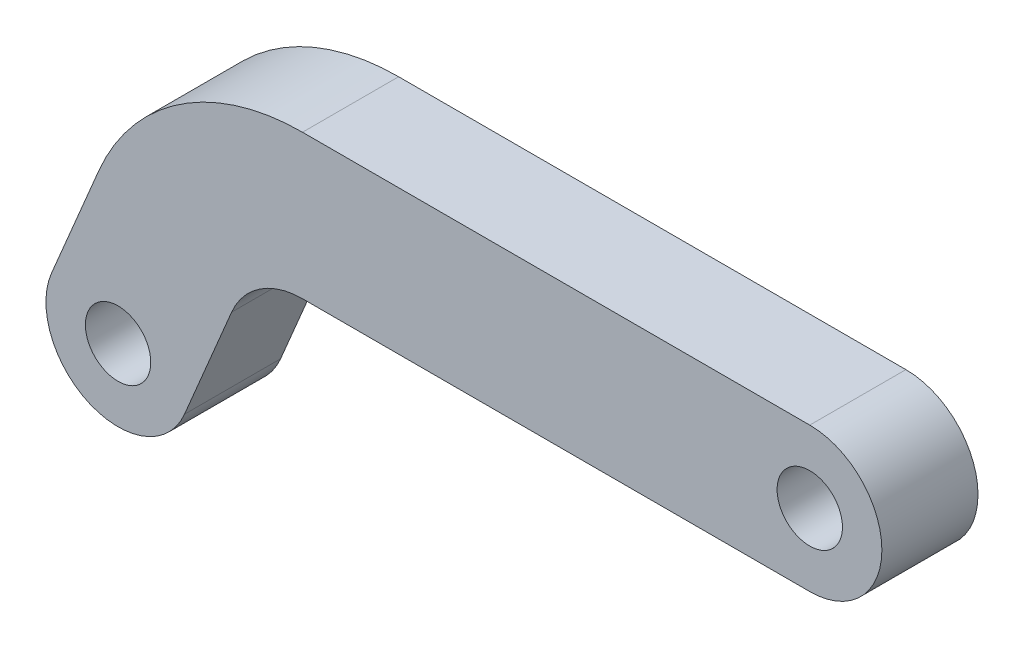
SolidWorks part; units mm, degrees
ref_plane "Front Plane" through (0, 0, 0) normal (0, 0, 1) x (1, 0, 0)
ref_plane "Top Plane" through (0, 0, 0) normal (0, 1, 0) x (1, 0, 0)
ref_plane "Right Plane" through (0, 0, 0) normal (1, 0, 0) x (0, 0, -1)
sketch "Sketch1" plane through (0, 0, 0) normal (0, 0, 1) x (1, 0, 0)
  line L0 (45.6947, 18.1841) -> (12.1852, 18.1841)
  line L2 (45.6947, 8.6591) -> (12.1852, 8.6591)
  line L3 (4.3895, -1.8476) -> (7.5031, 5.5498)
  line L4 (-4.3895, 1.8476) -> (-1.276, 9.2449)
  line L5 (0, 0) -> (45.6947, 13.4216) construction
  circle A0 centre (0, 0) radius 2.159
  circle A1 centre (45.6947, 13.4216) radius 2.159
  arc A2 (45.6947, 8.6591) -> (45.6947, 18.1841) centre (45.6947, 13.4216) ccw
  arc A4 (-4.3895, 1.8476) -> (4.3895, -1.8476) centre (0, 0) ccw
  arc A5 (12.1852, 8.6591) -> (7.5031, 5.5498) centre (12.1852, 3.5791) ccw
  arc A6 (12.1852, 18.1841) -> (-1.276, 9.2449) centre (12.1852, 3.5791) ccw
  point P9 (12.1852, 3.5791)
  dimension "D1" = 4.318
  dimension "D4" = 4.7625
  dimension "D5" = 4.7625
  dimension "D6" = 12.7
  dimension "D7" = 5.08
  dimension "D2" = 47.625
extrude "Boss-Extrude1" add sketch "Sketch1" along normal mid plane 6.35
